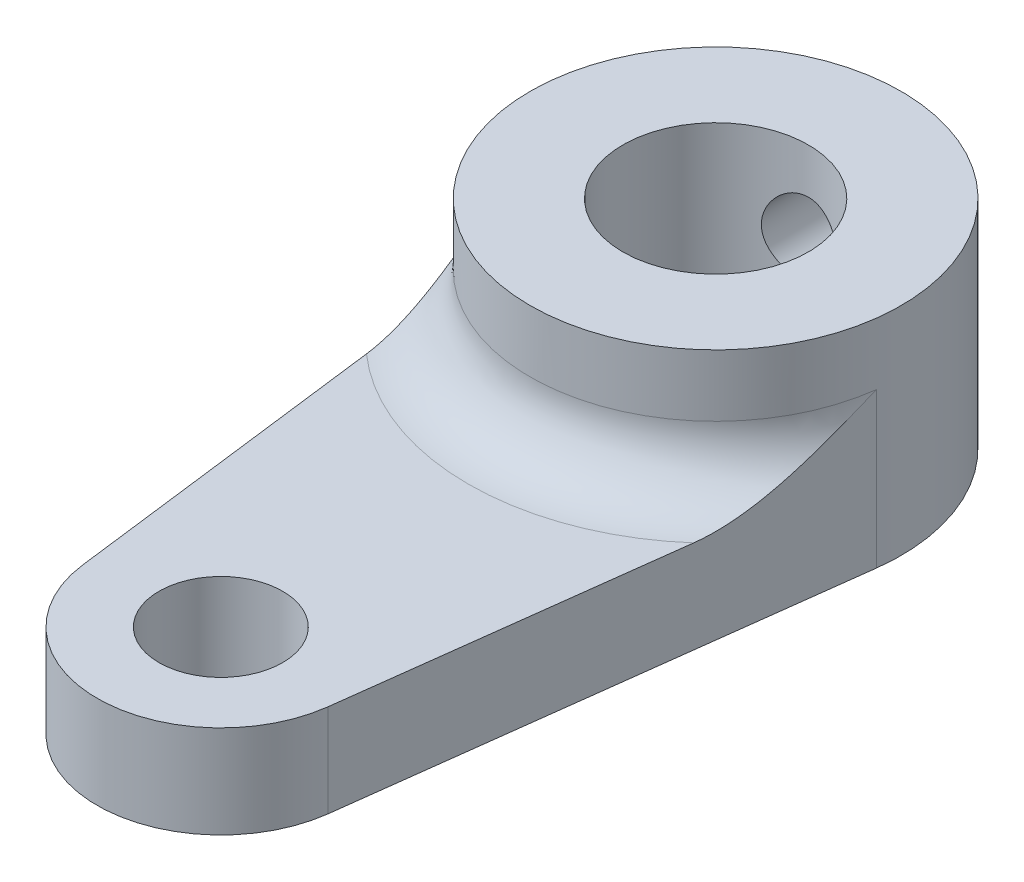
SolidWorks part; units mm, degrees
ref_plane "Front Plane" through (0, 0, 0) normal (0, 0, 1) x (1, 0, 0)
ref_plane "Top Plane" through (0, 0, 0) normal (0, 1, 0) x (1, 0, 0)
ref_plane "Right Plane" through (0, 0, 0) normal (1, 0, 0) x (0, 0, -1)
sketch "Sketch1" plane through (0, 0, 0) normal (0, 1, 0) x (1, 0, 0)
  line L0 (0, 0) -> (0, -16) construction
  line L1 (-5.9529, -0.75) -> (-3.9686, -16.5)
  line L2 (5.9529, -0.75) -> (3.9686, -16.5)
  circle A0 centre (0, 0) radius 6
  circle A1 centre (0, -16) radius 4
  circle A2 centre (0, -16) radius 2
  circle A3 centre (0, 0) radius 3
  dimension "D1" = 12
  dimension "D2" = 4
  dimension "D3" = 8
  dimension "D5" = 6
  dimension "D4" = 16
extrude "Boss-Extrude1" add sketch "Sketch1" along normal blind 3
sketch "Sketch2" plane through (0, 3, 0) normal (0, 1, 0) x (1, 0, 0)
  circle A0 centre (0, 0) radius 3 construction
  circle A1 centre (0, 0) radius 3
  circle A2 centre (0, 0) radius 6
  dimension "D1" = 12
extrude "Boss-Extrude2" add sketch "Sketch2" along normal blind 4
fillet "Fillet1" radius 2 1 edges at (0, 3, 6)
sketch "Sketch3" plane through (0, 0, 0) normal (0, -1, 0) x (1, 0, 0)
  line L0 (-6, -10) -> (6, -10)
  point P2 (0, -10)
  dimension "D1" = 12
  dimension "D2" = 10
surface "Surface-Extrude1" sketch "Sketch3" parameters "D1"=8
hole_wizard "M3 Tapped Hole2" positions "Sketch4" profile "Sketch5" tap size "M3" standard "ISO"
sketch "Sketch4" plane through (0, 0, -10) normal (0, 0, 1) x (1, 0, 0)
  point P0 (0, 4.2852)
  dimension "D1" = 4.2852
sketch "Sketch5" plane through (0, 4.2852, -10) normal (1, 0, 0) x (0, 1, 0)
  line L0 (0, 0) -> (0, 12.7511)
  line L1 (0, 12.7511) -> (1.25, 12)
  line L2 (1.25, 12) -> (1.25, 0.275)
  line L3 (1.25, 0.275) -> (1.525, 0)
  line L5 (1.525, 0) -> (0, 0)
  line L6 (-1.25, 0.275) -> (-1.525, 0) construction
  line L10 (0, 12.7511) -> (-1.25, 12) construction
  line L11 (0, -6.35) -> (0, 107.95) construction
  dimension "Tap Drill Dia." = 2.5
  dimension "Tap Drill Depth" = 12
  dimension "Near C'Sink Dia." = 3.05
  dimension "Near C'Sink Angle" = 90
  dimension "Drill Angle" = 118
cosmetic thread "Hole Thread1" parameters "D1"=6, "D2"=3
